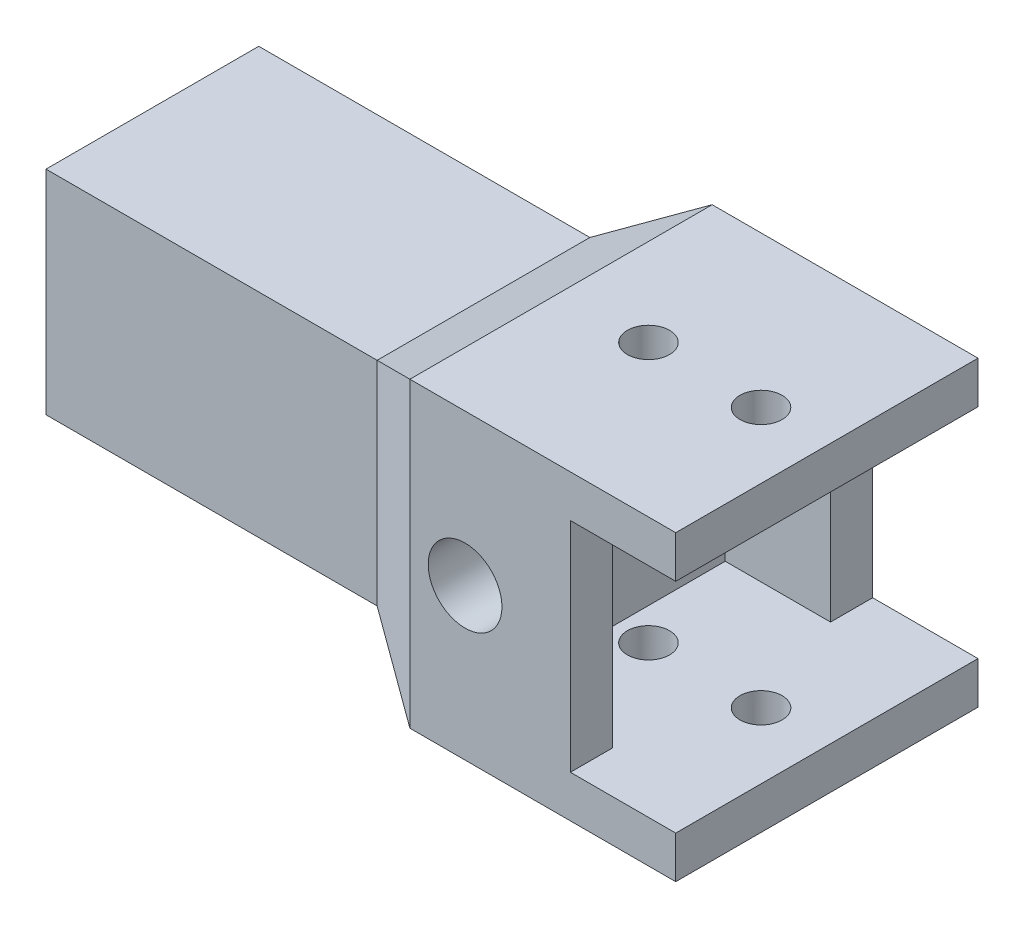
SolidWorks part; units mm, degrees
ref_plane "Front Plane" through (0, 0, 0) normal (0, 0, 1) x (1, 0, 0)
ref_plane "Top Plane" through (0, 0, 0) normal (0, 1, 0) x (1, 0, 0)
ref_plane "Right Plane" through (0, 0, 0) normal (1, 0, 0) x (0, 0, -1)
sketch "Sketch1" plane through (0, 0, 0) normal (1, 0, 0) x (0, 0, -1)
  line L1 (-10, 10) -> (10, 10)
  line L2 (-10, 10) -> (-10, -10)
  line L3 (-10, -10) -> (10, -10)
  line L4 (10, 10) -> (10, -10)
  line L5 (-10, 10) -> (10, -10) construction
  line L6 (-10, -10) -> (10, 10) construction
  point P0 (0, 0)
  dimension "D1" = 20
  dimension "D2" = 20
extrude "Boss-Extrude1" add sketch "Sketch1" along normal blind 20
sketch "Sketch2" plane through (20, 0, 0) normal (1, 0, 0) x (0, 0, -1)
  line L1 (-10, 20.1) -> (10, 20.1)
  line L2 (-10, 20.1) -> (-10, -20.1)
  line L3 (-10, -20.1) -> (10, -20.1)
  line L4 (10, 20.1) -> (10, -20.1)
  line L5 (-10, 20.1) -> (10, -20.1) construction
  line L6 (-10, -20.1) -> (10, 20.1) construction
  point P0 (0, 0)
  dimension "D1" = 20
  dimension "D2" = 40.2
extrude "Boss-Extrude2" add sketch "Sketch2" along normal blind 64.7
sketch "Sketch3" plane through (0, 0, 10) normal (0, 0, 1) x (1, 0, 0)
  line L1 (20, 20.1) -> (84.7, 20.1) construction
  line L2 (20, 20.1) -> (20, -20.1) construction
  line L3 (20, -20.1) -> (84.7, -20.1) construction
  line L4 (84.7, 20.1) -> (84.7, -20.1) construction
  line L5 (20, 20.1) -> (84.7, -20.1) construction
  line L6 (20, -20.1) -> (84.7, 20.1) construction
  line L7 (72.8, 10.4) -> (31.9, 10.4)
  line L8 (72.8, 10.4) -> (72.8, -10.4)
  line L9 (72.8, -10.4) -> (31.9, -10.4)
  line L10 (31.9, 10.4) -> (31.9, -10.4)
  line L11 (72.8, 10.4) -> (31.9, -10.4) construction
  line L12 (72.8, -10.4) -> (31.9, 10.4) construction
  point P4 (52.35, 0)
  point P7 (52.35, 0)
  dimension "D1" = 40.9
  dimension "D2" = 20.8
extrude "Cut-Extrude1" cut sketch "Sketch3" against normal through all
sketch "Sketch4" plane through (0, 0, 10) normal (0, 0, 1) x (1, 0, 0)
  line L0 (84.7, -20.1) -> (20, -20.1) construction
  line L1 (84.7, 20.1) -> (72.8, 20.1)
  line L2 (84.7, 20.1) -> (84.7, -20.1)
  line L3 (84.7, -20.1) -> (72.8, -20.1)
  line L4 (72.8, 20.1) -> (72.8, -20.1)
  line L5 (84.7, 20.1) -> (72.8, -20.1) construction
  line L6 (84.7, -20.1) -> (72.8, 20.1) construction
  point P4 (78.75, 0)
extrude "Cut-Extrude2" cut sketch "Sketch4" against normal through all
sketch "Sketch5" plane through (0, 0, 10) normal (0, 0, 1) x (1, 0, 0)
  line L0 (31.9, 0) -> (28.53, 0) construction
  line L5 (31.9, 10.4) -> (31.9, -10.4) construction
  line L7 (25.16, 0) -> (25.86, 0) construction
  line L8 (25.16, 9.4) -> (31.9, 9.4) construction
  line L9 (25.16, 9.4) -> (25.16, -9.4) construction
  line L10 (25.16, -9.4) -> (31.9, -9.4) construction
  line L11 (31.9, 9.4) -> (31.9, -9.4) construction
  line L12 (25.16, 9.4) -> (31.9, -9.4) construction
  line L13 (25.16, -9.4) -> (31.9, 9.4) construction
  line L14 (25.86, 0) -> (30.16, 0) construction
  line L15 (28.01, 0) -> (28.01, 9.4) construction
  line L16 (28.53, 9.4) -> (28.53, 7.1) construction
  line L17 (28.53, 7.1) -> (28.53, 2.7) construction
  line L18 (28.53, 2.7) -> (28.53, -2.7) construction
  line L19 (28.53, -2.7) -> (28.53, -7.1) construction
  line L20 (28.53, -7.1) -> (28.53, -9.4) construction
  line L21 (28.53, 4.9) -> (28.01, 4.9) construction
  circle A0 centre (28.01, 4.9) radius 2.35
  circle A1 centre (28.01, -4.9) radius 2.35
  dimension "D9" = 4.7
  dimension "D1" = 3.37
  dimension "D2" = 18.8
  dimension "D3" = 0.7
  dimension "D4" = 4.3
  dimension "D5" = 2.3
  dimension "D6" = 4.4
  dimension "D7" = 2.3
  dimension "D8" = 4.4
extrude "Cut-Extrude3" cut sketch "Sketch5" against normal blind 10
sketch "Sketch6" plane through (72.8, 0, 0) normal (1, 0, 0) x (0, 0, -1)
  line L0 (10, -10.4) -> (10, 10.4) construction
  line L1 (10, 0) -> (-3.0961, 0) construction
  line L3 (10, -10.4) -> (-10, -10.4) construction
  line L4 (10, -10.4) -> (10, -20.1) construction
  line L5 (10, -20.1) -> (-10, -20.1) construction
  line L6 (-10, -10.4) -> (-10, -20.1) construction
  line L7 (10, -10.4) -> (-10, -20.1) construction
  line L8 (10, -20.1) -> (-10, -10.4) construction
  circle A0 centre (0, -15.25) radius 2.35
  circle A1 centre (0, 15.25) radius 2.35
  point P10 (0, -15.25)
  dimension "D1" = 4.7
extrude "Cut-Extrude4" cut sketch "Sketch6" against normal blind 10
chamfer "Chamfer1" distance 1 angle 45 4 edges at (30.36, 4.9, 10) (25.66, -4.9, 10) (72.8, 15.25, 2.35) (72.8, -15.25, -2.35)
sketch "Sketch7" plane through (20, 0, 0) normal (-1, 0, 0) x (0, 0, 1)
  line L1 (10, 20.1) -> (-10, 20.1)
  line L2 (10, 20.1) -> (10, 10)
  line L3 (10, 10) -> (-10, 10)
  line L4 (-10, 20.1) -> (-10, 10)
  line L5 (10, 20.1) -> (-10, 10) construction
  line L6 (10, 10) -> (-10, 20.1) construction
  line L7 (10, -10) -> (-10, -10)
  line L8 (10, -10) -> (10, -20.1)
  line L9 (10, -20.1) -> (-10, -20.1)
  line L10 (-10, -10) -> (-10, -20.1)
  line L11 (10, -10) -> (-10, -20.1) construction
  line L12 (10, -20.1) -> (-10, -10) construction
  point P4 (0, 15.05)
  point P11 (0, -15.05)
extrude "Boss-Extrude4" add sketch "Sketch7" along normal blind 4.7
sketch "Sketch9" plane through (0, 0, 0) normal (-1, 0, 0) x (0, 0, 1)
  line L1 (10, 10) -> (-10, 10)
  line L2 (10, 10) -> (10, -10)
  line L3 (10, -10) -> (-10, -10)
  line L4 (-10, 10) -> (-10, -10)
  line L5 (10, 10) -> (-10, -10) construction
  line L6 (10, -10) -> (-10, 10) construction
  point P4 (0, 0)
extrude "Boss-Extrude5" add sketch "Sketch9" along normal blind 24.7
sketch "Sketch10" plane through (-24.7, 0, 0) normal (-1, 0, 0) x (0, 0, 1)
  circle A0 centre (0, 0) radius 3
  dimension "D1" = 6
extrude "Cut-Extrude5" cut sketch "Sketch10" against normal blind 2
fillet "Fillet1" radius 3.23 1 edges at (-22.7, 0, 3)
sketch "Sketch11" plane through (-24.7, 0, 0) normal (-1, 0, 0) x (0, 0, 1)
  line L5 (-10, -10) -> (10, -10)
  line L6 (-10, -10) -> (-10, 10)
  line L7 (-10, 10) -> (10, 10)
  line L8 (10.1, -10.1) -> (10.1, 10.1)
  line L9 (10.1, 10.1) -> (-10.1, 10.1)
  line L10 (-10.1, 10.1) -> (-10.1, -10.1)
  line L11 (-10.1, -10.1) -> (10.1, -10.1)
  line L12 (10.1, -10.1) -> (10.1, 10.1)
  line L13 (10.1, 10.1) -> (-10.1, 10.1)
  line L14 (-10.1, 10.1) -> (-10.1, -10.1)
  line L15 (-10.1, -10.1) -> (10.1, -10.1)
  line L16 (10, -10) -> (10, 10)
  line L17 (-10, -10) -> (10, 10) construction
  line L18 (-10, 10) -> (10, -10) construction
  point P4 (0, 0)
  dimension "D1" = 0.1
extrude "Boss-Extrude6" add sketch "Sketch11" against normal up to surface (40 mm away) up to face at (15.3, 15.05, 0)
sketch "Sketch12" plane through (0, 0, 10) normal (0, 0, 1) x (1, 0, 0)
  line L0 (72.8, 20.1) -> (15.3, 20.1)
  line L1 (15.3, 20.1) -> (15.3, -20.1)
  line L2 (15.3, -20.1) -> (72.8, -20.1)
  line L3 (72.8, -20.1) -> (72.8, -10.4)
  line L4 (72.8, -10.4) -> (31.9, -10.4)
  line L5 (31.9, -10.4) -> (31.9, 10.4)
  line L6 (31.9, 10.4) -> (72.8, 10.4)
  line L7 (72.8, 10.4) -> (72.8, 20.1)
  circle A1 centre (28.01, 4.9) radius 3.35
  circle A2 centre (28.01, -4.9) radius 3.35
extrude "Boss-Extrude7" add sketch "Sketch12" along normal blind 0.1
sketch "Sketch13" plane through (0, 0, -10) normal (0, 0, -1) x (-1, 0, 0)
  line L0 (-72.8, -20.1) -> (-15.3, -20.1)
  line L1 (-15.3, -20.1) -> (-15.3, 20.1)
  line L2 (-15.3, 20.1) -> (-72.8, 20.1)
  line L3 (-72.8, 20.1) -> (-72.8, 10.4)
  line L4 (-72.8, 10.4) -> (-31.9, 10.4)
  line L5 (-31.9, 10.4) -> (-31.9, -10.4)
  line L6 (-31.9, -10.4) -> (-72.8, -10.4)
  line L7 (-72.8, -10.4) -> (-72.8, -20.1)
extrude "Boss-Extrude8" add sketch "Sketch13" along normal blind 0.1
sketch "Sketch14" plane through (72.8, 0, 0) normal (1, 0, 0) x (0, 0, -1)
  line L1 (12.5227, 25.4986) -> (-15.3185, 25.4986)
  line L2 (12.5227, 25.4986) -> (12.5227, -25.1297)
  line L3 (12.5227, -25.1297) -> (-15.3185, -25.1297)
  line L4 (-15.3185, 25.4986) -> (-15.3185, -25.1297)
  line L5 (12.5227, 25.4986) -> (-15.3185, -25.1297) construction
  line L6 (12.5227, -25.1297) -> (-15.3185, 25.4986) construction
  point P4 (-1.3979, 0.1845)
extrude "Cut-Extrude6" cut sketch "Sketch14" against normal up to surface (57.5 mm away) up to face at (15.3, -15.1, 0)
sketch "Sketch18" plane through (15.3, 0, 0) normal (1, 0, 0) x (0, 0, -1)
  line L8 (14.35, -14.35) -> (14.35, 14.35)
  line L9 (14.35, 14.35) -> (-14.35, 14.35)
  line L10 (-14.35, 14.35) -> (-14.35, -14.35)
  line L11 (-14.35, -14.35) -> (14.35, -14.35)
  line L12 (14.35, -14.35) -> (14.35, 14.35)
  line L13 (14.35, 14.35) -> (-14.35, 14.35)
  line L14 (-14.35, 14.35) -> (-14.35, -14.35)
  line L15 (-14.35, -14.35) -> (14.35, -14.35)
  line L20 (10.35, -10.35) -> (10.35, 10.35)
  line L21 (10.35, 10.35) -> (-10.35, 10.35)
  line L22 (-10.35, 10.35) -> (-10.35, -10.35)
  line L23 (-10.35, -10.35) -> (10.35, -10.35)
  line L24 (10.35, -10.35) -> (10.35, 10.35)
  line L25 (10.35, 10.35) -> (-10.35, 10.35)
  line L26 (-10.35, 10.35) -> (-10.35, -10.35)
  line L27 (-10.35, -10.35) -> (10.35, -10.35)
  point P4 (0, 0)
  dimension "D1" = 4.25
  dimension "D2" = 0.25
extrude "Boss-Extrude10" add sketch "Sketch18" along normal blind 10 and the other way blind 0.96
sketch "Sketch19" plane through (15.3, 0, 0) normal (1, 0, 0) x (0, 0, -1)
  line L12 (10.35, -10.35) -> (10.35, 10.35)
  line L13 (10.35, 10.35) -> (-10.35, 10.35)
  line L14 (-10.35, 10.35) -> (-10.35, -10.35)
  line L15 (-10.35, -10.35) -> (10.35, -10.35)
  line L16 (10.35, -10.35) -> (10.35, 10.35)
  line L17 (10.35, 10.35) -> (-10.35, 10.35)
  line L18 (-10.35, 10.35) -> (-10.35, -10.35)
  line L19 (-10.35, -10.35) -> (10.35, -10.35)
  point P4 (0, 0)
  dimension "D1" = 0.25
extrude "Boss-Extrude11" add sketch "Sketch19" along normal blind 4.04
sketch "Sketch21" plane through (15.3, 0, 0) normal (-1, 0, 0) x (0, 0, 1)
  line L1 (10.35, 10.35) -> (-10.35, 10.35)
  line L2 (10.35, 10.35) -> (10.35, -10.35)
  line L3 (10.35, -10.35) -> (-10.35, -10.35)
  line L4 (-10.35, 10.35) -> (-10.35, -10.35)
  line L5 (10.35, 10.35) -> (-10.35, -10.35) construction
  line L6 (10.35, -10.35) -> (-10.35, 10.35) construction
  point P4 (0, 0)
extrude "Boss-Extrude13" add sketch "Sketch21" along normal up to surface (0.96 mm away) up to face at (14.34, 0, 0)
sketch "Sketch22" plane through (25.3, 0, 0) normal (1, 0, 0) x (0, 0, -1)
  line L1 (14.35, 14.35) -> (-14.35, 14.35)
  line L2 (14.35, 14.35) -> (14.35, -14.35)
  line L3 (14.35, -14.35) -> (-14.35, -14.35)
  line L4 (-14.35, 14.35) -> (-14.35, -14.35)
  line L5 (14.35, 14.35) -> (-14.35, -14.35) construction
  line L6 (14.35, -14.35) -> (-14.35, 14.35) construction
  line L7 (10.35, 10.35) -> (-10.35, 10.35)
  line L8 (10.35, 10.35) -> (10.35, -10.35)
  line L9 (10.35, -10.35) -> (-10.35, -10.35)
  line L10 (-10.35, 10.35) -> (-10.35, -10.35)
  line L11 (10.35, 10.35) -> (-10.35, -10.35) construction
  line L12 (10.35, -10.35) -> (-10.35, 10.35) construction
  point P4 (0, 0)
  point P11 (0, 0)
extrude "Boss-Extrude14" add sketch "Sketch22" along normal blind 14.04
chamfer "Chamfer2" distance 7.6 angle 30 4 edges at (14.34, -10.1, 0) (14.34, 0, -10.1) (14.34, 10.1, 0) (14.34, 0, 10.1) first distance on face at (-5.18, -10.1, 0) first distance on face at (-5.18, 0, -10.1) first distance on face at (-5.18, 10.1, 0) first distance on face at (-5.18, 0, 10.1)
sketch "Sketch24" plane through (0, 0, 14.35) normal (0, 0, 1) x (1, 0, 0)
  line L0 (14.1012, -14.35) -> (39.34, -14.35) construction
  line L1 (39.34, 14.35) -> (19.34, 14.35) construction
  line L2 (39.34, 14.35) -> (39.34, -14.35) construction
  line L3 (39.34, -14.35) -> (19.34, -14.35) construction
  line L4 (19.34, 14.35) -> (19.34, -14.35) construction
  line L5 (39.34, 14.35) -> (19.34, -14.35) construction
  line L6 (39.34, -14.35) -> (19.34, 14.35) construction
  circle A0 centre (19.34, 0) radius 3.5
  point P4 (29.34, 0)
  dimension "D2" = 7
  dimension "D1" = 20
extrude "Cut-Extrude7" cut sketch "Sketch24" against normal through all
sketch "Sketch25" plane through (39.34, 0, 0) normal (1, 0, 0) x (0, 0, -1)
  line L0 (-14.35, 14.35) -> (-14.35, -14.35) construction
  line L1 (-10.35, 10.35) -> (-14.35, 10.35)
  line L2 (-10.35, 10.35) -> (-10.35, -10.35)
  line L3 (-10.35, -10.35) -> (-14.35, -10.35)
  line L4 (-14.35, 10.35) -> (-14.35, -10.35)
  line L5 (-10.35, 10.35) -> (-14.35, -10.35) construction
  line L6 (-10.35, -10.35) -> (-14.35, 10.35) construction
  line L7 (14.35, -14.35) -> (14.35, 14.35) construction
  line L8 (10.35, 10.35) -> (14.35, 10.35)
  line L9 (10.35, 10.35) -> (10.35, -10.35)
  line L10 (10.35, -10.35) -> (14.35, -10.35)
  line L11 (14.35, 10.35) -> (14.35, -10.35)
  line L12 (10.35, 10.35) -> (14.35, -10.35) construction
  line L13 (10.35, -10.35) -> (14.35, 10.35) construction
  point P4 (-12.35, 0)
  point P12 (12.35, 0)
extrude "Cut-Extrude8" cut sketch "Sketch25" against normal blind 10
sketch "Sketch26" plane through (0, 14.35, 0) normal (0, 1, 0) x (1, 0, 0)
  line L0 (39.34, 0) -> (33.09, 0) construction
  line L1 (39.34, 14.35) -> (14.1012, 14.35) construction
  line L2 (39.34, 14.35) -> (39.34, -14.35) construction
  line L3 (39.34, -14.35) -> (14.1012, -14.35) construction
  line L4 (14.1012, 14.35) -> (14.1012, -14.35) construction
  line L5 (39.34, 14.35) -> (14.1012, -14.35) construction
  line L6 (39.34, -14.35) -> (14.1012, 14.35) construction
  line L7 (33.09, 0) -> (22.4012, 0) construction
  line L8 (22.4012, 0) -> (14.1012, 0) construction
  circle A0 centre (33.09, 0) radius 2
  circle A1 centre (22.4012, 0) radius 2
  point P4 (26.7206, 0)
  dimension "D3" = 4
  dimension "D4" = 4
  dimension "D1" = 6.25
  dimension "D2" = 8.3
extrude "Cut-Extrude9" cut sketch "Sketch26" against normal through all
